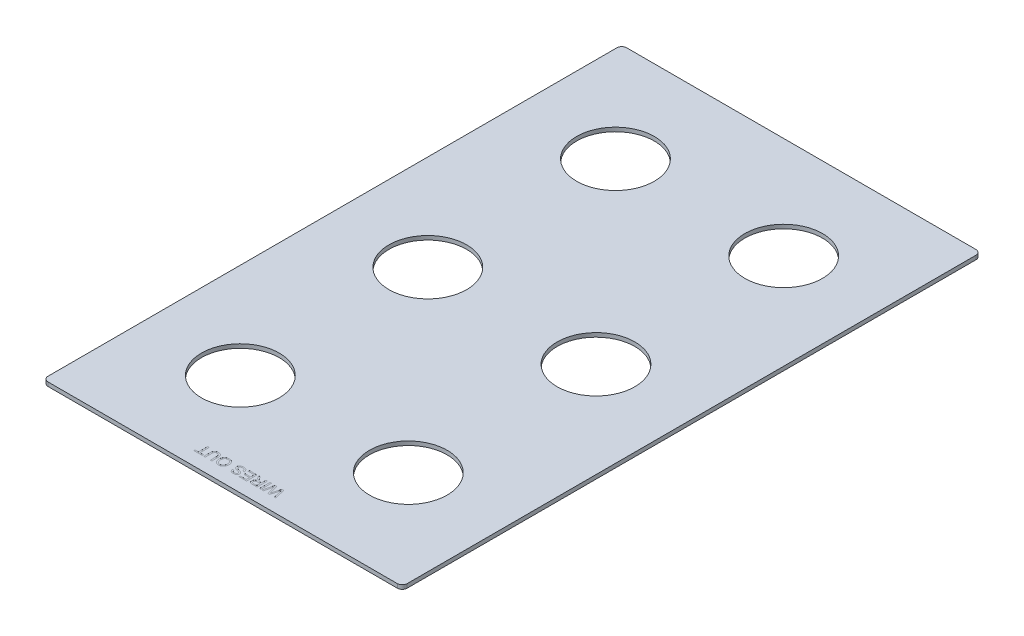
SolidWorks part; units mm, degrees
ref_plane "Front" through (0, 0, 0) normal (0, 0, 1) x (1, 0, 0)
ref_plane "Top" through (0, 0, 0) normal (0, 1, 0) x (1, 0, 0)
ref_plane "Right" through (0, 0, 0) normal (1, 0, 0) x (0, 0, -1)
sketch "Sketch1" plane through (0, 0, 0) normal (0, 1, 0) x (1, 0, 0)
  line L0 (-78.1178, -119.38) -> (-78.2448, -119.38) construction
  line L1 (-111.125, 184.15) -> (111.125, 184.15)
  line L2 (-114.3, 180.975) -> (-114.3, -180.975)
  line L3 (-111.125, -184.15) -> (111.125, -184.15)
  line L4 (114.3, 180.975) -> (114.3, -180.975)
  line L5 (-114.3, 184.15) -> (114.3, -184.15) construction
  line L6 (-114.3, -184.15) -> (114.3, 184.15) construction
  circle A0 centre (53.5178, -119.5086) radius 24.727
  circle A1 centre (53.5178, -0.0643) radius 24.727
  circle A2 centre (-53.5178, -119.38) radius 24.727
  circle A3 centre (-53.5178, -0.0643) radius 24.727
  circle A4 centre (-53.5178, 119.38) radius 24.727
  circle A5 centre (53.5178, 119.38) radius 24.727
  arc A6 (-64.6679, -97.452) -> (-49.567, -143.6607) centre (-53.5178, -119.38) ccw construction
  arc A7 (-64.6679, -97.452) -> (-42.3677, -141.308) centre (-53.5178, -119.38) ccw construction
  arc A8 (114.3, 180.975) -> (111.125, 184.15) centre (111.125, 180.975) ccw
  arc A9 (-114.3, 180.975) -> (-111.125, 184.15) centre (-111.125, 180.975) cw
  arc A10 (-114.3, -180.975) -> (-111.125, -184.15) centre (-111.125, -180.975) ccw
  arc A11 (111.125, -184.15) -> (114.3, -180.975) centre (111.125, -180.975) ccw
  point P0 (0, 0)
  dimension "D3" = 0.127
  dimension "D4" = 3.175
  dimension "D1" = 228.6
  dimension "D2" = 368.3
extrude "Boss-Extrude1" add sketch "Sketch1" along normal blind 2.54
sketch "Sketch2" plane through (0, 2.54, 0) normal (0, 1, 0) x (1, 0, 0)
  line L0 (0, -184.15) -> (0, -168.91) construction
  line L1 (-111.125, -184.15) -> (111.125, -184.15) construction
  line L2 (25.4, -168.91) -> (-25.4, -168.91) construction
  text T0 "WIRES OUT" font "Arial" height in points 26
  point P7 (0, -168.91)
  dimension "D1" = 15.24
  dimension "D2" = 50.8
extrude "Cut-Extrude2" cut sketch "Sketch2" against normal blind 0.0254
sketch "Sketch3" plane through (0, 2.54, 0) normal (0, 1, 0) x (1, 0, 0)
  line L0 (53.5178, -144.2356) -> (53.5178, -184.15) construction
  line L1 (-111.125, -184.15) -> (111.125, -184.15) construction
  line L2 (53.5178, 144.107) -> (53.5178, 184.15) construction
  line L3 (111.125, 184.15) -> (-111.125, 184.15) construction
  circle A0 centre (53.5178, -119.5086) radius 24.727 construction
  circle A1 centre (53.5178, 119.38) radius 24.727 construction
